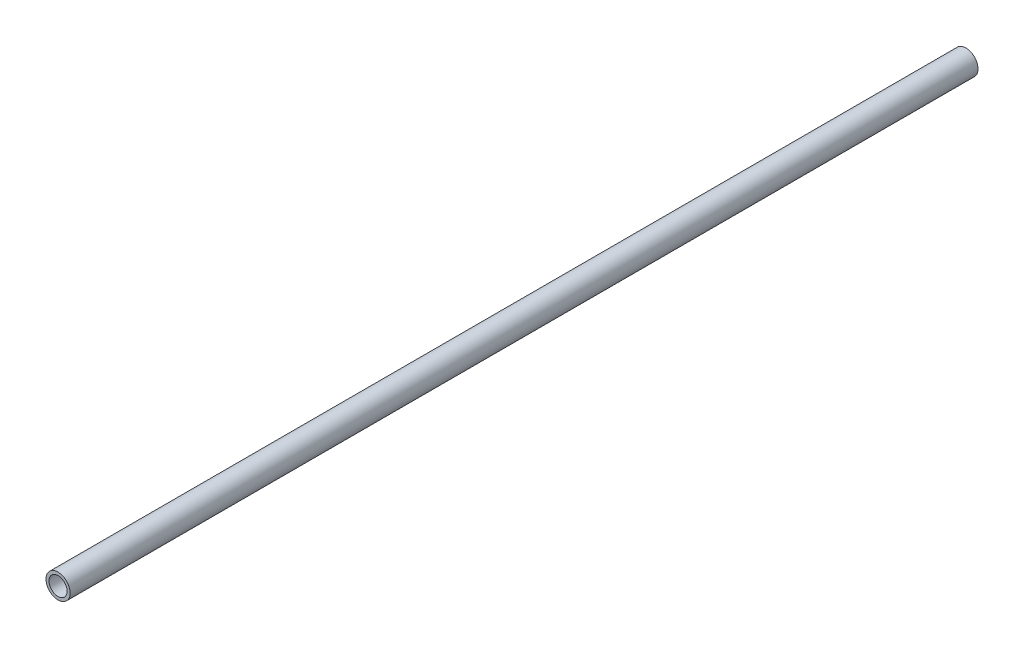
SolidWorks part; units mm, degrees
material "Thornel Mat VMA"
ref_plane "Front Plane" through (0, 0, 0) normal (0, 0, 1) x (1, 0, 0)
ref_plane "Top Plane" through (0, 0, 0) normal (0, 1, 0) x (1, 0, 0)
ref_plane "Right Plane" through (0, 0, 0) normal (1, 0, 0) x (0, 0, -1)
sketch "Sketch1" plane through (0, 0, 0) normal (0, 0, 1) x (1, 0, 0)
  circle A0 centre (0, 0) radius 2
  circle A1 centre (0, 0) radius 1.5
  dimension "D1" = 4
  dimension "D2" = 3
extrude "Boss-Extrude1" add sketch "Sketch1" along normal blind 150.288
